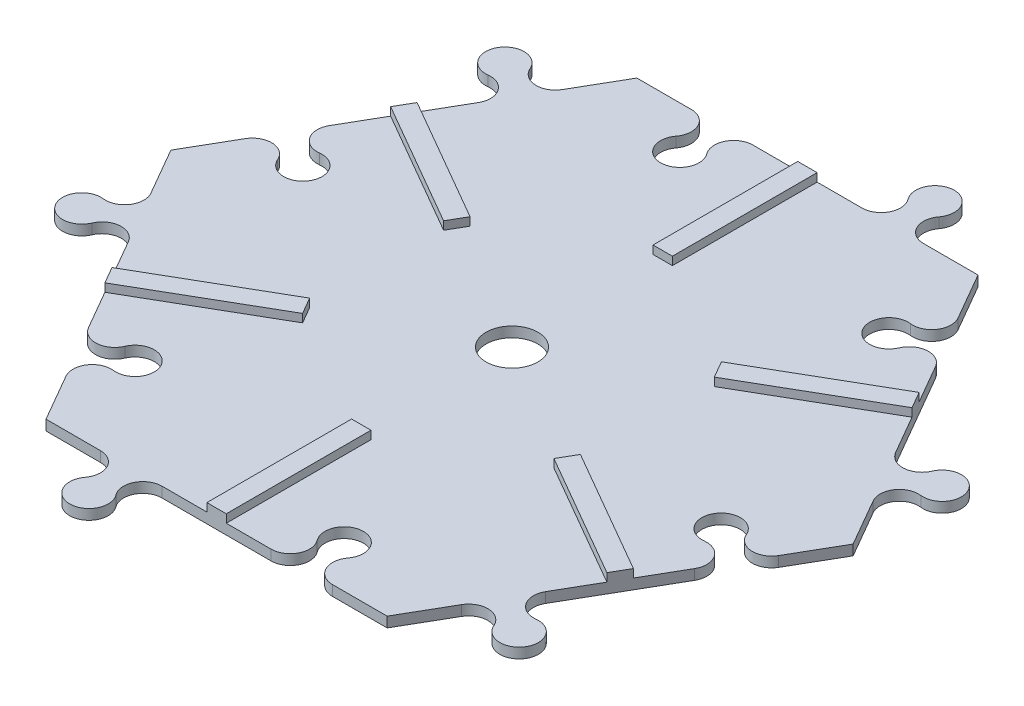
SolidWorks part; units mm, degrees
ref_plane "Front Plane" through (0, 0, 0) normal (0, 0, 1) x (1, 0, 0)
ref_plane "Top Plane" through (0, 0, 0) normal (0, 1, 0) x (1, 0, 0)
ref_plane "Right Plane" through (0, 0, 0) normal (1, 0, 0) x (0, 0, -1)
sketch "Sketch1" plane through (0, 0, 0) normal (0, 1, 0) x (1, 0, 0)
  line L10 (52.7929, -91.44) -> (105.5858, 0)
  line L11 (105.5858, 0) -> (52.7929, 91.44)
  line L12 (52.7929, 91.44) -> (-52.7929, 91.44)
  line L13 (-52.7929, 91.44) -> (-105.5858, 0)
  line L14 (-105.5858, 0) -> (-52.7929, -91.44)
  line L15 (-52.7929, -91.44) -> (52.7929, -91.44)
  circle A3 centre (0, 0) radius 91.44 construction
  dimension "D1" = 182.88
extrude "Boss-Extrude1" add sketch "Sketch1" along normal blind 3.175 contours L14 L15 L10 L11 L12 L13
sketch "Sketch2" plane through (0, 0, 0) normal (0, 1, 0) x (1, 0, 0)
  line L0 (-16.8715, 91.44) -> (-35.9215, 91.44)
  line L1 (0, 0) -> (0, 91.44) construction
  line L2 (0, 91.44) -> (52.7929, 91.44) construction
  line L4 (26.3965, 91.44) -> (26.3965, 114.3) construction
  line L5 (16.8715, 91.44) -> (35.9215, 91.44)
  line L7 (52.7929, 91.44) -> (-52.7929, 91.44) construction
  arc A0 (-31.159, 100.965) -> (-26.3965, 110.49) centre (-26.3965, 104.5369) cw construction
  arc A1 (-21.634, 100.965) -> (-26.3965, 110.49) centre (-26.3965, 104.5369) ccw construction
  arc A2 (-16.8715, 91.44) -> (-21.634, 100.965) centre (-16.8715, 97.3931) cw construction
  arc A3 (16.8715, 91.44) -> (21.634, 100.965) centre (16.8715, 97.3931) ccw
  arc A4 (-35.9215, 91.44) -> (-31.159, 100.965) centre (-35.9215, 97.3931) ccw construction
  arc A5 (21.634, 100.965) -> (26.3965, 110.49) centre (26.3965, 104.5369) cw
  arc A7 (35.9215, 91.44) -> (31.159, 100.965) centre (35.9215, 97.3931) cw
  arc A8 (31.159, 100.965) -> (26.3965, 110.49) centre (26.3965, 104.5369) ccw
  arc A9 (-16.8715, 91.44) -> (-21.634, 81.915) centre (-16.8715, 85.4869) ccw
  arc A10 (-21.634, 81.915) -> (-26.3965, 72.39) centre (-26.3965, 78.3431) cw
  arc A11 (-31.159, 81.915) -> (-26.3965, 72.39) centre (-26.3965, 78.3431) ccw
  arc A12 (-35.9215, 91.44) -> (-31.159, 81.915) centre (-35.9215, 85.4869) cw
  dimension "D1" = 22.86
  dimension "D3" = 19.05
  dimension "D4" = 19.05
extrude "Boss-Extrude2" add sketch "Sketch2" along normal up to surface (3.175 mm away) contours A7 A8 A5 A3 L5 up to face at (0, 3.175, 0)
extrude "Cut-Extrude2" cut sketch "Sketch2<3>" along normal through all contours A11 A10 A9 L0 A12
sketch "Sketch2<3>" plane through (0, 0, 0) normal (0, 1, 0) x (1, 0, 0) same geometry as "Sketch2"
sketch "Sketch3" [suppressed] plane through (0, 0, 0) normal (0, 0, 1) x (1, 0, 0)
  line L0 (0, 0) -> (0, 25.4) construction
  dimension "D1" = 25.4
pattern_circular "CirPattern1" count 6 over 360 about axis through (0, 0, 0) along (0, 1, 0) of "Boss-Extrude2", "Cut-Extrude2" reverse direction yes
sketch "Sketch4" plane through (0, 3.175, 0) normal (0, 1, 0) x (1, 0, 0)
  circle A0 centre (0, 0) radius 8.001
  dimension "D1" = 16.002
extrude "Cut-Extrude3" cut sketch "Sketch4" against normal up to surface (3.175 mm away) up to face at (0, 0, 0)
sketch "Sketch5" plane through (0, 3.175, 0) normal (0, 1, 0) x (1, 0, 0)
  line L0 (-80.6894, -43.1219) -> (-41.8984, -20.726)
  line L1 (-77.6894, -48.3181) -> (-38.8984, -25.9221)
  line L2 (-87.6251, -31.1089) -> (-70.7536, -60.3311) construction
  line L3 (-79.1894, -45.72) -> (-20.0775, -11.5918) construction
  line L5 (-87.6251, -31.1089) -> (-70.7536, -60.3311) construction
  line L6 (-80.6894, -43.1219) -> (-77.6894, -48.3181)
  line L7 (-38.8984, -25.9221) -> (-41.8984, -20.726)
  dimension "D2" = 44.7919
  dimension "D1" = 6
extrude "Boss-Extrude3" add sketch "Sketch5" along normal blind 2.54 contours L6 L3 L7 L0 | L3 L6 L1 L7 region at (-60.5439, 3.175, 33.223) region at (-59.0439, 3.175, 35.8211)
pattern_circular "CirPattern2" count 6 over 360 about axis through (0, -22.6302, 0) along (0, 1, 0) of "Boss-Extrude3"
sketch "Sketch6" plane through (0, 3.175, 0) normal (0, 1, 0) x (1, 0, 0)
  line L0 (-77.6894, 48.3181) -> (-38.8984, 25.9221) construction
  line L3 (-3, 46.6481) -> (-3, 91.44) construction
  line L4 (-3, 91.44) -> (-16.8715, 91.44) construction
  line L5 (-35.9215, 91.44) -> (-52.7929, 91.44) construction
  line L6 (-52.7929, 91.44) -> (-61.2286, 76.8289) construction
  line L7 (-70.7536, 60.3311) -> (-77.6894, 48.3181) construction
  line L9 (-41.8984, 20.726) -> (-80.6894, 43.1219) construction
  line L10 (-80.6894, 43.1219) -> (-87.6251, 31.1089) construction
  line L11 (-97.1501, 14.6111) -> (-105.5858, 0) construction
  line L12 (-105.5858, 0) -> (-97.1501, -14.6111) construction
  line L13 (-87.6251, -31.1089) -> (-80.6894, -43.1219) construction
  line L14 (-80.6894, -43.1219) -> (-41.8984, -20.726) construction
  line L15 (-38.8984, -25.9221) -> (-41.8984, -20.726)
  line L16 (-3, -91.44) -> (-3, -46.6481) construction
  line L19 (-38.8984, -25.9221) -> (-77.6894, -48.3181) construction
  line L20 (-77.6894, -48.3181) -> (-70.7536, -60.3311) construction
  line L21 (-61.2286, -76.8289) -> (-52.7929, -91.44) construction
  line L22 (-52.7929, -91.44) -> (-35.9215, -91.44) construction
  line L23 (-16.8715, -91.44) -> (-3, -91.44) construction
  line L24 (77.6894, -48.3181) -> (38.8984, -25.9221) construction
  line L27 (3, -46.6481) -> (3, -91.44) construction
  line L28 (3, -91.44) -> (16.8715, -91.44) construction
  line L29 (35.9215, -91.44) -> (52.7929, -91.44) construction
  line L30 (52.7929, -91.44) -> (61.2286, -76.8289) construction
  line L31 (70.7536, -60.3311) -> (77.6894, -48.3181) construction
  line L32 (80.6894, 43.1219) -> (41.8984, 20.726) construction
  line L35 (41.8984, -20.726) -> (80.6894, -43.1219) construction
  line L36 (80.6894, -43.1219) -> (87.6251, -31.1089) construction
  line L37 (97.1501, -14.6111) -> (105.5858, 0) construction
  line L38 (105.5858, 0) -> (97.1501, 14.6111) construction
  line L39 (87.6251, 31.1089) -> (80.6894, 43.1219) construction
  line L40 (3, 91.44) -> (3, 46.6481) construction
  line L43 (38.8984, 25.9221) -> (77.6894, 48.3181) construction
  line L44 (77.6894, 48.3181) -> (70.7536, 60.3311) construction
  line L45 (61.2286, 76.8289) -> (52.7929, 91.44) construction
  line L46 (52.7929, 91.44) -> (35.9215, 91.44) construction
  line L47 (16.8715, 91.44) -> (3, 91.44) construction
  line L48 (-77.6894, 48.3181) -> (-38.8984, 25.9221)
  line L51 (-3, 46.6481) -> (-3, 91.44)
  line L52 (-3, 91.44) -> (-16.8715, 91.44)
  line L53 (-35.9215, 91.44) -> (-52.7929, 91.44)
  line L54 (-52.7929, 91.44) -> (-61.2286, 76.8289)
  line L55 (-70.7536, 60.3311) -> (-77.6894, 48.3181)
  line L57 (-41.8984, 20.726) -> (-80.6894, 43.1219)
  line L58 (-80.6894, 43.1219) -> (-87.6251, 31.1089)
  line L59 (-97.1501, 14.6111) -> (-105.5858, 0)
  line L60 (-105.5858, 0) -> (-97.1501, -14.6111)
  line L61 (-87.6251, -31.1089) -> (-80.6894, -43.1219)
  line L62 (-80.6894, -43.1219) -> (-41.8984, -20.726)
  line L63 (-38.8984, 25.9221) -> (-41.8984, 20.726)
  line L64 (-3, -91.44) -> (-3, -46.6481)
  line L66 (-3, 46.6481) -> (3, 46.6481)
  line L67 (-38.8984, -25.9221) -> (-77.6894, -48.3181)
  line L68 (-77.6894, -48.3181) -> (-70.7536, -60.3311)
  line L69 (-61.2286, -76.8289) -> (-52.7929, -91.44)
  line L70 (-52.7929, -91.44) -> (-35.9215, -91.44)
  line L71 (-16.8715, -91.44) -> (-3, -91.44)
  line L72 (77.6894, -48.3181) -> (38.8984, -25.9221)
  line L75 (3, -46.6481) -> (3, -91.44)
  line L76 (3, -91.44) -> (16.8715, -91.44)
  line L77 (35.9215, -91.44) -> (52.7929, -91.44)
  line L78 (52.7929, -91.44) -> (61.2286, -76.8289)
  line L79 (70.7536, -60.3311) -> (77.6894, -48.3181)
  line L80 (80.6894, 43.1219) -> (41.8984, 20.726)
  line L83 (41.8984, -20.726) -> (80.6894, -43.1219)
  line L84 (80.6894, -43.1219) -> (87.6251, -31.1089)
  line L85 (97.1501, -14.6111) -> (105.5858, 0)
  line L86 (105.5858, 0) -> (97.1501, 14.6111)
  line L87 (87.6251, 31.1089) -> (80.6894, 43.1219)
  line L88 (3, 91.44) -> (3, 46.6481)
  line L91 (38.8984, 25.9221) -> (77.6894, 48.3181)
  line L92 (77.6894, 48.3181) -> (70.7536, 60.3311)
  line L93 (61.2286, 76.8289) -> (52.7929, 91.44)
  line L94 (52.7929, 91.44) -> (35.9215, 91.44)
  line L95 (16.8715, 91.44) -> (3, 91.44)
  line L96 (38.8984, 25.9221) -> (41.8984, 20.726)
  line L97 (41.8984, -20.726) -> (38.8984, -25.9221)
  line L98 (-3, -46.6481) -> (3, -46.6481)
  arc A1 (-16.8715, 91.44) -> (-21.634, 81.915) centre (-16.8715, 85.4869) ccw construction
  arc A2 (-31.159, 81.915) -> (-21.634, 81.915) centre (-26.3965, 78.3431) ccw construction
  arc A3 (-31.159, 81.915) -> (-35.9215, 91.44) centre (-35.9215, 85.4869) ccw construction
  arc A4 (-71.8588, 77.4669) -> (-61.2286, 76.8289) centre (-66.3842, 79.8055) ccw construction
  arc A5 (-71.8588, 77.4669) -> (-76.6213, 69.2181) centre (-77.3334, 75.1284) ccw construction
  arc A6 (-70.7536, 60.3311) -> (-76.6213, 69.2181) centre (-75.9092, 63.3077) ccw construction
  arc A7 (-87.6251, 31.1089) -> (-81.7574, 22.2219) centre (-82.4695, 28.1323) ccw construction
  arc A8 (-86.5199, 13.9731) -> (-81.7574, 22.2219) centre (-81.0454, 16.3116) ccw construction
  arc A9 (-86.5199, 13.9731) -> (-97.1501, 14.6111) centre (-91.9945, 11.6345) ccw construction
  arc A10 (-103.0177, -23.4981) -> (-97.1501, -14.6111) centre (-102.3056, -17.5877) ccw construction
  arc A11 (-103.0177, -23.4981) -> (-98.2552, -31.7469) centre (-103.7298, -29.4084) ccw construction
  arc A12 (-87.6251, -31.1089) -> (-98.2552, -31.7469) centre (-92.7806, -34.0855) ccw construction
  arc A15 (-70.7536, -60.3311) -> (-60.1235, -59.6931) centre (-65.5981, -57.3545) ccw construction
  arc A16 (-55.361, -67.9419) -> (-60.1235, -59.6931) centre (-54.6489, -62.0316) ccw construction
  arc A17 (-55.361, -67.9419) -> (-61.2286, -76.8289) centre (-56.0731, -73.8523) ccw construction
  arc A18 (-31.159, -100.965) -> (-35.9215, -91.44) centre (-35.9215, -97.3931) ccw construction
  arc A19 (-31.159, -100.965) -> (-21.634, -100.965) centre (-26.3965, -104.5369) ccw construction
  arc A20 (-16.8715, -91.44) -> (-21.634, -100.965) centre (-16.8715, -97.3931) ccw construction
  arc A22 (16.8715, -91.44) -> (21.634, -81.915) centre (16.8715, -85.4869) ccw construction
  arc A23 (31.159, -81.915) -> (21.634, -81.915) centre (26.3965, -78.3431) ccw construction
  arc A24 (31.159, -81.915) -> (35.9215, -91.44) centre (35.9215, -85.4869) ccw construction
  arc A25 (71.8588, -77.4669) -> (61.2286, -76.8289) centre (66.3842, -79.8055) ccw construction
  arc A26 (71.8588, -77.4669) -> (76.6213, -69.2181) centre (77.3334, -75.1284) ccw construction
  arc A27 (70.7536, -60.3311) -> (76.6213, -69.2181) centre (75.9092, -63.3077) ccw construction
  arc A29 (87.6251, -31.1089) -> (81.7574, -22.2219) centre (82.4695, -28.1323) ccw construction
  arc A30 (86.5199, -13.9731) -> (81.7574, -22.2219) centre (81.0454, -16.3116) ccw construction
  arc A31 (86.5199, -13.9731) -> (97.1501, -14.6111) centre (91.9945, -11.6345) ccw construction
  arc A32 (103.0177, 23.4981) -> (97.1501, 14.6111) centre (102.3056, 17.5877) ccw construction
  arc A33 (103.0177, 23.4981) -> (98.2552, 31.7469) centre (103.7298, 29.4084) ccw construction
  arc A34 (87.6251, 31.1089) -> (98.2552, 31.7469) centre (92.7806, 34.0855) ccw construction
  arc A36 (70.7536, 60.3311) -> (60.1235, 59.6931) centre (65.5981, 57.3545) ccw construction
  arc A37 (55.361, 67.9419) -> (60.1235, 59.6931) centre (54.6489, 62.0316) ccw construction
  arc A38 (55.361, 67.9419) -> (61.2286, 76.8289) centre (56.0731, 73.8523) ccw construction
  arc A39 (31.159, 100.965) -> (35.9215, 91.44) centre (35.9215, 97.3931) ccw construction
  arc A40 (31.159, 100.965) -> (21.634, 100.965) centre (26.3965, 104.5369) ccw construction
  arc A41 (16.8715, 91.44) -> (21.634, 100.965) centre (16.8715, 97.3931) ccw construction
  arc A43 (-16.8715, 91.44) -> (-21.634, 81.915) centre (-16.8715, 85.4869) ccw
  arc A44 (-31.159, 81.915) -> (-21.634, 81.915) centre (-26.3965, 78.3431) ccw
  arc A45 (-31.159, 81.915) -> (-35.9215, 91.44) centre (-35.9215, 85.4869) ccw
  arc A46 (-71.8588, 77.4669) -> (-61.2286, 76.8289) centre (-66.3842, 79.8055) ccw
  arc A47 (-71.8588, 77.4669) -> (-76.6213, 69.2181) centre (-77.3334, 75.1284) ccw
  arc A48 (-70.7536, 60.3311) -> (-76.6213, 69.2181) centre (-75.9092, 63.3077) ccw
  arc A49 (-87.6251, 31.1089) -> (-81.7574, 22.2219) centre (-82.4695, 28.1323) ccw
  arc A50 (-86.5199, 13.9731) -> (-81.7574, 22.2219) centre (-81.0454, 16.3116) ccw
  arc A51 (-86.5199, 13.9731) -> (-97.1501, 14.6111) centre (-91.9945, 11.6345) ccw
  arc A52 (-103.0177, -23.4981) -> (-97.1501, -14.6111) centre (-102.3056, -17.5877) ccw
  arc A53 (-103.0177, -23.4981) -> (-98.2552, -31.7469) centre (-103.7298, -29.4084) ccw
  arc A54 (-87.6251, -31.1089) -> (-98.2552, -31.7469) centre (-92.7806, -34.0855) ccw
  arc A57 (-70.7536, -60.3311) -> (-60.1235, -59.6931) centre (-65.5981, -57.3545) ccw
  arc A58 (-55.361, -67.9419) -> (-60.1235, -59.6931) centre (-54.6489, -62.0316) ccw
  arc A59 (-55.361, -67.9419) -> (-61.2286, -76.8289) centre (-56.0731, -73.8523) ccw
  arc A60 (-31.159, -100.965) -> (-35.9215, -91.44) centre (-35.9215, -97.3931) ccw
  arc A61 (-31.159, -100.965) -> (-21.634, -100.965) centre (-26.3965, -104.5369) ccw
  arc A62 (-16.8715, -91.44) -> (-21.634, -100.965) centre (-16.8715, -97.3931) ccw
  arc A64 (16.8715, -91.44) -> (21.634, -81.915) centre (16.8715, -85.4869) ccw
  arc A65 (31.159, -81.915) -> (21.634, -81.915) centre (26.3965, -78.3431) ccw
  arc A66 (31.159, -81.915) -> (35.9215, -91.44) centre (35.9215, -85.4869) ccw
  arc A67 (71.8588, -77.4669) -> (61.2286, -76.8289) centre (66.3842, -79.8055) ccw
  arc A68 (71.8588, -77.4669) -> (76.6213, -69.2181) centre (77.3334, -75.1284) ccw
  arc A69 (70.7536, -60.3311) -> (76.6213, -69.2181) centre (75.9092, -63.3077) ccw
  arc A71 (87.6251, -31.1089) -> (81.7574, -22.2219) centre (82.4695, -28.1323) ccw
  arc A72 (86.5199, -13.9731) -> (81.7574, -22.2219) centre (81.0454, -16.3116) ccw
  arc A73 (86.5199, -13.9731) -> (97.1501, -14.6111) centre (91.9945, -11.6345) ccw
  arc A74 (103.0177, 23.4981) -> (97.1501, 14.6111) centre (102.3056, 17.5877) ccw
  arc A75 (103.0177, 23.4981) -> (98.2552, 31.7469) centre (103.7298, 29.4084) ccw
  arc A76 (87.6251, 31.1089) -> (98.2552, 31.7469) centre (92.7806, 34.0855) ccw
  arc A78 (70.7536, 60.3311) -> (60.1235, 59.6931) centre (65.5981, 57.3545) ccw
  arc A79 (55.361, 67.9419) -> (60.1235, 59.6931) centre (54.6489, 62.0316) ccw
  arc A80 (55.361, 67.9419) -> (61.2286, 76.8289) centre (56.0731, 73.8523) ccw
  arc A81 (31.159, 100.965) -> (35.9215, 91.44) centre (35.9215, 97.3931) ccw
  arc A82 (31.159, 100.965) -> (21.634, 100.965) centre (26.3965, 104.5369) ccw
  arc A83 (16.8715, 91.44) -> (21.634, 100.965) centre (16.8715, 97.3931) ccw
sketch "Sketch7" plane through (0, 3.175, 0) normal (0, 1, 0) x (1, 0, 0)
  line L42 (-3, -46.6481) -> (3, -46.6481)
  line L43 (3, -46.6481) -> (3, -91.44)
  line L44 (3, -91.44) -> (16.8715, -91.44)
  line L45 (35.9215, -91.44) -> (52.7929, -91.44)
  line L46 (52.7929, -91.44) -> (61.2286, -76.8289)
  line L47 (70.7536, -60.3311) -> (77.6894, -48.3181)
  line L48 (77.6894, -48.3181) -> (38.8984, -25.9221)
  line L49 (38.8984, -25.9221) -> (41.8984, -20.726)
  line L50 (41.8984, -20.726) -> (80.6894, -43.1219)
  line L51 (80.6894, -43.1219) -> (87.6251, -31.1089)
  line L52 (97.1501, -14.6111) -> (105.5858, 0)
  line L53 (105.5858, 0) -> (97.1501, 14.6111)
  line L54 (87.6251, 31.1089) -> (80.6894, 43.1219)
  line L55 (80.6894, 43.1219) -> (41.8984, 20.726)
  line L56 (41.8984, 20.726) -> (38.8984, 25.9221)
  line L57 (38.8984, 25.9221) -> (77.6894, 48.3181)
  line L58 (77.6894, 48.3181) -> (70.7536, 60.3311)
  line L59 (61.2286, 76.8289) -> (52.7929, 91.44)
  line L60 (52.7929, 91.44) -> (35.9215, 91.44)
  line L61 (16.8715, 91.44) -> (3, 91.44)
  line L62 (3, 91.44) -> (3, 46.6481)
  line L63 (3, 46.6481) -> (-3, 46.6481)
  line L64 (-3, 46.6481) -> (-3, 91.44)
  line L65 (-3, 91.44) -> (-16.8715, 91.44)
  line L66 (-35.9215, 91.44) -> (-52.7929, 91.44)
  line L67 (-52.7929, 91.44) -> (-61.2286, 76.8289)
  line L68 (-70.7536, 60.3311) -> (-77.6894, 48.3181)
  line L69 (-77.6894, 48.3181) -> (-38.8984, 25.9221)
  line L70 (-38.8984, 25.9221) -> (-41.8984, 20.726)
  line L71 (-41.8984, 20.726) -> (-80.6894, 43.1219)
  line L72 (-80.6894, 43.1219) -> (-87.6251, 31.1089)
  line L73 (-97.1501, 14.6111) -> (-105.5858, 0)
  line L74 (-105.5858, 0) -> (-97.1501, -14.6111)
  line L75 (-87.6251, -31.1089) -> (-80.6894, -43.1219)
  line L76 (-80.6894, -43.1219) -> (-41.8984, -20.726)
  line L77 (-41.8984, -20.726) -> (-38.8984, -25.9221)
  line L78 (-38.8984, -25.9221) -> (-77.6894, -48.3181)
  line L79 (-77.6894, -48.3181) -> (-70.7536, -60.3311)
  line L80 (-61.2286, -76.8289) -> (-52.7929, -91.44)
  line L81 (-52.7929, -91.44) -> (-35.9215, -91.44)
  line L82 (-16.8715, -91.44) -> (-3, -91.44)
  line L83 (-3, -91.44) -> (-3, -46.6481)
  line L86 (-16.8715, -91.44) -> (16.8715, -91.44)
  line L87 (35.9215, -91.44) -> (52.7929, -91.44)
  line L88 (52.7929, -91.44) -> (61.2286, -76.8289)
  line L93 (70.7536, -60.3311) -> (87.6251, -31.1089)
  line L94 (97.1501, -14.6111) -> (105.5858, 0)
  line L95 (105.5858, 0) -> (97.1501, 14.6111)
  line L100 (87.6251, 31.1089) -> (70.7536, 60.3311)
  line L101 (61.2286, 76.8289) -> (52.7929, 91.44)
  line L102 (52.7929, 91.44) -> (35.9215, 91.44)
  line L107 (16.8715, 91.44) -> (-16.8715, 91.44)
  line L108 (-35.9215, 91.44) -> (-52.7929, 91.44)
  line L109 (-52.7929, 91.44) -> (-61.2286, 76.8289)
  line L114 (-70.7536, 60.3311) -> (-87.6251, 31.1089)
  line L115 (-97.1501, 14.6111) -> (-105.5858, 0)
  line L116 (-105.5858, 0) -> (-97.1501, -14.6111)
  line L121 (-87.6251, -31.1089) -> (-70.7536, -60.3311)
  line L122 (-61.2286, -76.8289) -> (-52.7929, -91.44)
  line L123 (-52.7929, -91.44) -> (-35.9215, -91.44)
  circle A0 centre (0, 0) radius 8.001 construction
  circle A1 centre (0, 0) radius 8.001
  arc A36 (16.8715, -91.44) -> (21.634, -81.915) centre (16.8715, -85.4869) ccw
  arc A37 (31.159, -81.915) -> (21.634, -81.915) centre (26.3965, -78.3431) ccw
  arc A38 (31.159, -81.915) -> (35.9215, -91.44) centre (35.9215, -85.4869) ccw
  arc A39 (71.8588, -77.4669) -> (61.2286, -76.8289) centre (66.3842, -79.8055) ccw
  arc A40 (71.8588, -77.4669) -> (76.6213, -69.2181) centre (77.3334, -75.1284) ccw
  arc A41 (70.7536, -60.3311) -> (76.6213, -69.2181) centre (75.9092, -63.3077) ccw
  arc A42 (87.6251, -31.1089) -> (81.7574, -22.2219) centre (82.4695, -28.1323) ccw
  arc A43 (86.5199, -13.9731) -> (81.7574, -22.2219) centre (81.0454, -16.3116) ccw
  arc A44 (86.5199, -13.9731) -> (97.1501, -14.6111) centre (91.9945, -11.6345) ccw
  arc A45 (103.0177, 23.4981) -> (97.1501, 14.6111) centre (102.3056, 17.5877) ccw
  arc A46 (103.0177, 23.4981) -> (98.2552, 31.7469) centre (103.7298, 29.4084) ccw
  arc A47 (87.6251, 31.1089) -> (98.2552, 31.7469) centre (92.7806, 34.0855) ccw
  arc A48 (70.7536, 60.3311) -> (60.1235, 59.6931) centre (65.5981, 57.3545) ccw
  arc A49 (55.361, 67.9419) -> (60.1235, 59.6931) centre (54.6489, 62.0316) ccw
  arc A50 (55.361, 67.9419) -> (61.2286, 76.8289) centre (56.0731, 73.8523) ccw
  arc A51 (31.159, 100.965) -> (35.9215, 91.44) centre (35.9215, 97.3931) ccw
  arc A52 (31.159, 100.965) -> (21.634, 100.965) centre (26.3965, 104.5369) ccw
  arc A53 (16.8715, 91.44) -> (21.634, 100.965) centre (16.8715, 97.3931) ccw
  arc A54 (-16.8715, 91.44) -> (-21.634, 81.915) centre (-16.8715, 85.4869) ccw
  arc A55 (-31.159, 81.915) -> (-21.634, 81.915) centre (-26.3965, 78.3431) ccw
  arc A56 (-31.159, 81.915) -> (-35.9215, 91.44) centre (-35.9215, 85.4869) ccw
  arc A57 (-71.8588, 77.4669) -> (-61.2286, 76.8289) centre (-66.3842, 79.8055) ccw
  arc A58 (-71.8588, 77.4669) -> (-76.6213, 69.2181) centre (-77.3334, 75.1284) ccw
  arc A59 (-70.7536, 60.3311) -> (-76.6213, 69.2181) centre (-75.9092, 63.3077) ccw
  arc A60 (-87.6251, 31.1089) -> (-81.7574, 22.2219) centre (-82.4695, 28.1323) ccw
  arc A61 (-86.5199, 13.9731) -> (-81.7574, 22.2219) centre (-81.0454, 16.3116) ccw
  arc A62 (-86.5199, 13.9731) -> (-97.1501, 14.6111) centre (-91.9945, 11.6345) ccw
  arc A63 (-103.0177, -23.4981) -> (-97.1501, -14.6111) centre (-102.3056, -17.5877) ccw
  arc A64 (-103.0177, -23.4981) -> (-98.2552, -31.7469) centre (-103.7298, -29.4084) ccw
  arc A65 (-87.6251, -31.1089) -> (-98.2552, -31.7469) centre (-92.7806, -34.0855) ccw
  arc A66 (-70.7536, -60.3311) -> (-60.1235, -59.6931) centre (-65.5981, -57.3545) ccw
  arc A67 (-55.361, -67.9419) -> (-60.1235, -59.6931) centre (-54.6489, -62.0316) ccw
  arc A68 (-55.361, -67.9419) -> (-61.2286, -76.8289) centre (-56.0731, -73.8523) ccw
  arc A69 (-31.159, -100.965) -> (-35.9215, -91.44) centre (-35.9215, -97.3931) ccw
  arc A70 (-31.159, -100.965) -> (-21.634, -100.965) centre (-26.3965, -104.5369) ccw
  arc A71 (-16.8715, -91.44) -> (-21.634, -100.965) centre (-16.8715, -97.3931) ccw
  arc A72 (16.8715, -91.44) -> (21.634, -81.915) centre (16.8715, -85.4869) ccw
  arc A73 (31.159, -81.915) -> (21.634, -81.915) centre (26.3965, -78.3431) ccw
  arc A74 (31.159, -81.915) -> (35.9215, -91.44) centre (35.9215, -85.4869) ccw
  arc A75 (71.8588, -77.4669) -> (61.2286, -76.8289) centre (66.3842, -79.8055) ccw
  arc A76 (71.8588, -77.4669) -> (76.6213, -69.2181) centre (77.3334, -75.1284) ccw
  arc A77 (70.7536, -60.3311) -> (76.6213, -69.2181) centre (75.9092, -63.3077) ccw
  arc A78 (87.6251, -31.1089) -> (81.7574, -22.2219) centre (82.4695, -28.1323) ccw
  arc A79 (86.5199, -13.9731) -> (81.7574, -22.2219) centre (81.0454, -16.3116) ccw
  arc A80 (86.5199, -13.9731) -> (97.1501, -14.6111) centre (91.9945, -11.6345) ccw
  arc A81 (103.0177, 23.4981) -> (97.1501, 14.6111) centre (102.3056, 17.5877) ccw
  arc A82 (103.0177, 23.4981) -> (98.2552, 31.7469) centre (103.7298, 29.4084) ccw
  arc A83 (87.6251, 31.1089) -> (98.2552, 31.7469) centre (92.7806, 34.0855) ccw
  arc A84 (70.7536, 60.3311) -> (60.1235, 59.6931) centre (65.5981, 57.3545) ccw
  arc A85 (55.361, 67.9419) -> (60.1235, 59.6931) centre (54.6489, 62.0316) ccw
  arc A86 (55.361, 67.9419) -> (61.2286, 76.8289) centre (56.0731, 73.8523) ccw
  arc A87 (31.159, 100.965) -> (35.9215, 91.44) centre (35.9215, 97.3931) ccw
  arc A88 (31.159, 100.965) -> (21.634, 100.965) centre (26.3965, 104.5369) ccw
  arc A89 (16.8715, 91.44) -> (21.634, 100.965) centre (16.8715, 97.3931) ccw
  arc A90 (-16.8715, 91.44) -> (-21.634, 81.915) centre (-16.8715, 85.4869) ccw
  arc A91 (-31.159, 81.915) -> (-21.634, 81.915) centre (-26.3965, 78.3431) ccw
  arc A92 (-31.159, 81.915) -> (-35.9215, 91.44) centre (-35.9215, 85.4869) ccw
  arc A93 (-71.8588, 77.4669) -> (-61.2286, 76.8289) centre (-66.3842, 79.8055) ccw
  arc A94 (-71.8588, 77.4669) -> (-76.6213, 69.2181) centre (-77.3334, 75.1284) ccw
  arc A95 (-70.7536, 60.3311) -> (-76.6213, 69.2181) centre (-75.9092, 63.3077) ccw
  arc A96 (-87.6251, 31.1089) -> (-81.7574, 22.2219) centre (-82.4695, 28.1323) ccw
  arc A97 (-86.5199, 13.9731) -> (-81.7574, 22.2219) centre (-81.0454, 16.3116) ccw
  arc A98 (-86.5199, 13.9731) -> (-97.1501, 14.6111) centre (-91.9945, 11.6345) ccw
  arc A99 (-103.0177, -23.4981) -> (-97.1501, -14.6111) centre (-102.3056, -17.5877) ccw
  arc A100 (-103.0177, -23.4981) -> (-98.2552, -31.7469) centre (-103.7298, -29.4084) ccw
  arc A101 (-87.6251, -31.1089) -> (-98.2552, -31.7469) centre (-92.7806, -34.0855) ccw
  arc A102 (-70.7536, -60.3311) -> (-60.1235, -59.6931) centre (-65.5981, -57.3545) ccw
  arc A103 (-55.361, -67.9419) -> (-60.1235, -59.6931) centre (-54.6489, -62.0316) ccw
  arc A104 (-55.361, -67.9419) -> (-61.2286, -76.8289) centre (-56.0731, -73.8523) ccw
  arc A105 (-31.159, -100.965) -> (-35.9215, -91.44) centre (-35.9215, -97.3931) ccw
  arc A106 (-31.159, -100.965) -> (-21.634, -100.965) centre (-26.3965, -104.5369) ccw
  arc A107 (-16.8715, -91.44) -> (-21.634, -100.965) centre (-16.8715, -97.3931) ccw
  dimension "D1" = 0
